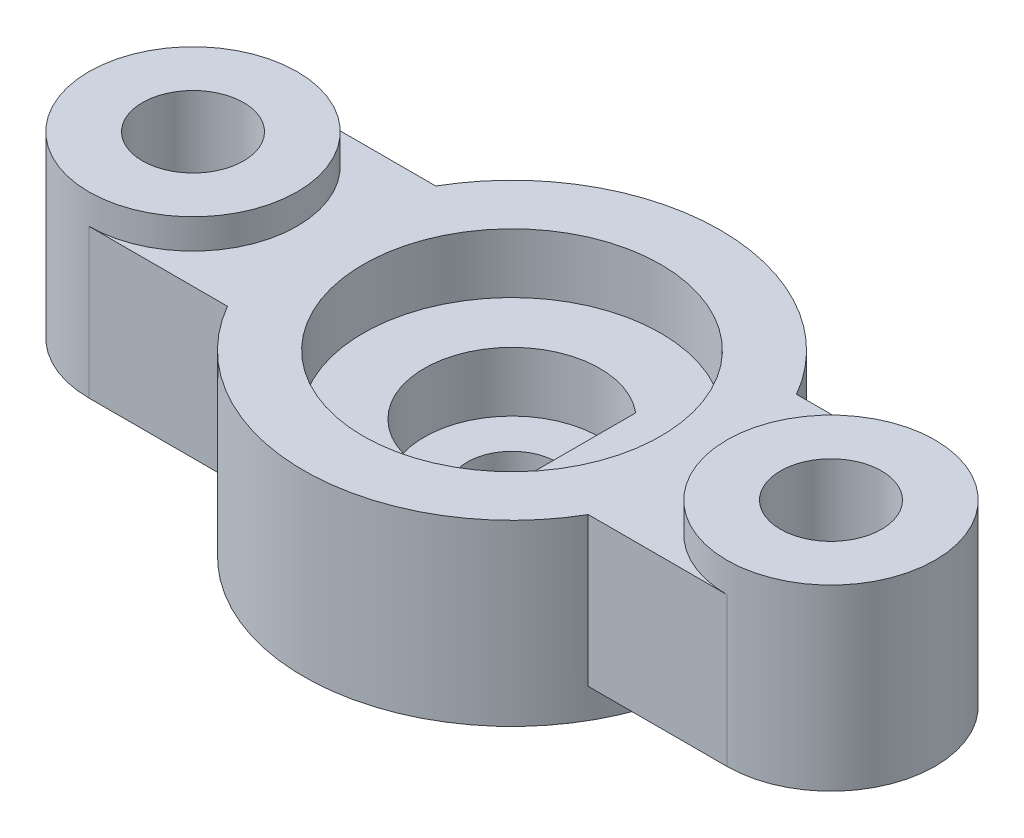
SolidWorks part; units mm, degrees
ref_plane "Plan de face" through (0, 0, 0) normal (0, 0, 1) x (1, 0, 0)
ref_plane "Plan de dessus" through (0, 0, 0) normal (0, 1, 0) x (1, 0, 0)
ref_plane "Plan de droite" through (0, 0, 0) normal (1, 0, 0) x (0, 0, -1)
sketch "Esquisse1" plane through (0, 0, 0) normal (0, 1, 0) x (1, 0, 0)
  line L0 (-10.72, 3.5) -> (-6.0622, 3.5)
  line L1 (-10.72, -3.5) -> (-6.0622, -3.5)
  line L2 (10.72, 3.5) -> (6.0622, 3.5)
  line L4 (10.72, -3.5) -> (6.0622, -3.5)
  circle A0 centre (0, 0) radius 5
  arc A1 (6.0622, 3.5) -> (-6.0622, 3.5) centre (0, 0) ccw
  circle A2 centre (10.72, 0) radius 1.7
  circle A3 centre (-10.72, 0) radius 1.7
  arc A4 (-10.72, 3.5) -> (-10.72, -3.5) centre (-10.72, 0) ccw
  arc A5 (10.72, -3.5) -> (10.72, 3.5) centre (10.72, 0) ccw
  arc A7 (-6.0622, -3.5) -> (6.0622, -3.5) centre (0, 0) ccw
  dimension "D1" = 14
  dimension "D2" = 10
  dimension "D5" = 3.4
  dimension "D6" = 3.4
  dimension "D7" = 7
  dimension "D8" = 7
  dimension "D3" = 10.72
  dimension "D4" = 10.72
  dimension "D9" = 0
extrude "Boss.-Extru.1" add sketch "Esquisse1" along normal blind 5
sketch "Esquisse2" plane through (0, 5, 0) normal (0, 1, 0) x (1, 0, 0)
  circle A0 centre (-10.72, 0) radius 3.5
  circle A1 centre (-10.72, 0) radius 1.7
  circle A2 centre (10.72, 0) radius 1.7
  circle A3 centre (10.72, 0) radius 3.5
  circle A4 centre (-10.72, 0) radius 1.7 construction
  circle A5 centre (10.72, 0) radius 1.7 construction
extrude "Boss.-Extru.2" add sketch "Esquisse2" along normal blind 1
sketch "Esquisse3" plane through (0, 0, 0) normal (0, -1, 0) x (1, 0, 0)
  circle A0 centre (0, 0) radius 7
  circle A1 centre (0, 0) radius 1.5
  dimension "D1" = 3
extrude "Boss.-Extru.3" add sketch "Esquisse3" along normal blind 1 and the other way blind 3
sketch "Esquisse6" plane through (0, 3, 0) normal (0, 1, 0) x (1, 0, 0)
  line L0 (1.9, 2.2567) -> (1.9, -2.2567)
  arc A0 (1.9, 2.2567) -> (1.9, -2.2567) centre (0, 0) ccw
  circle A1 centre (0, 0) radius 1.45 construction
  dimension "D1" = 5.9
  dimension "D2" = 2.9
  dimension "D3" = 1.9
extrude "Enlèv. mat.-Extru.1" cut sketch "Esquisse6" against normal blind 2
